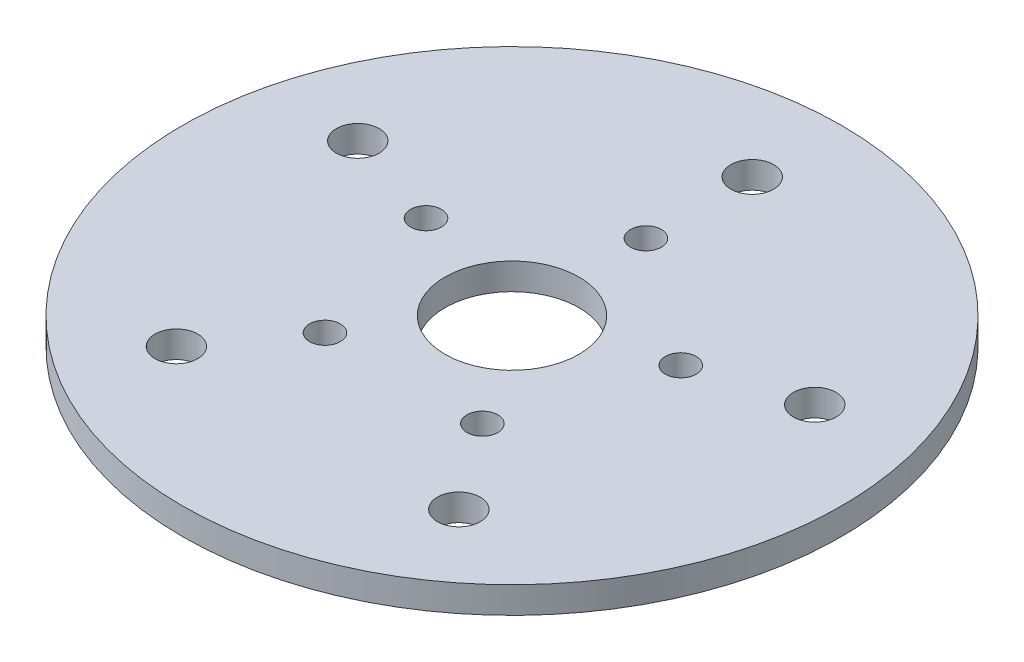
SolidWorks part; units mm, degrees
material "6061 Alloy"
ref_plane "Front Plane" through (0, 0, 0) normal (0, 0, 1) x (1, 0, 0)
ref_plane "Top Plane" through (0, 0, 0) normal (0, 1, 0) x (1, 0, 0)
ref_plane "Right Plane" through (0, 0, 0) normal (1, 0, 0) x (0, 0, -1)
sketch "Sketch1" plane through (0, 807.1164, 0) normal (0, 1, 0) x (-1, 0, 0)
  circle A0 centre (0, 0) radius 39.37
  dimension "D1" = 78.74
extrude "Boss-Extrude1" add sketch "Sketch1" against normal blind 3.175
sketch "Sketch2" plane through (0, 807.1164, 0) normal (0, 1, 0) x (1, 0, 0)
  line L0 (0, 0) -> (0, 16) construction
  line L1 (0, 0) -> (0, 28.702) construction
  circle A0 centre (0, 0) radius 8.001
  circle A1 centre (0, 0) radius 39.37 construction
  circle A2 centre (0, 16) radius 1.8415
  circle A3 centre (15.2169, 4.9443) radius 1.8415
  circle A4 centre (9.4046, -12.9443) radius 1.8415
  circle A5 centre (-9.4046, -12.9443) radius 1.8415
  circle A6 centre (-15.2169, 4.9443) radius 1.8415
  circle A7 centre (0, 28.702) radius 2.5527
  circle A8 centre (27.2972, 8.8694) radius 2.5527
  circle A9 centre (16.8706, -23.2204) radius 2.5527
  circle A10 centre (-16.8706, -23.2204) radius 2.5527
  circle A11 centre (-27.2972, 8.8694) radius 2.5527
  point P27 (0, 0)
  dimension "D1" = 16.002
  dimension "D2" = 3.683
  dimension "D6" = 5.1054
  dimension "D3" = 16
  dimension "D5" = 28.702
  dimension "D4" = 5
  dimension "D7" = 5
extrude "Cut-Extrude1" cut sketch "Sketch2" against normal through all
